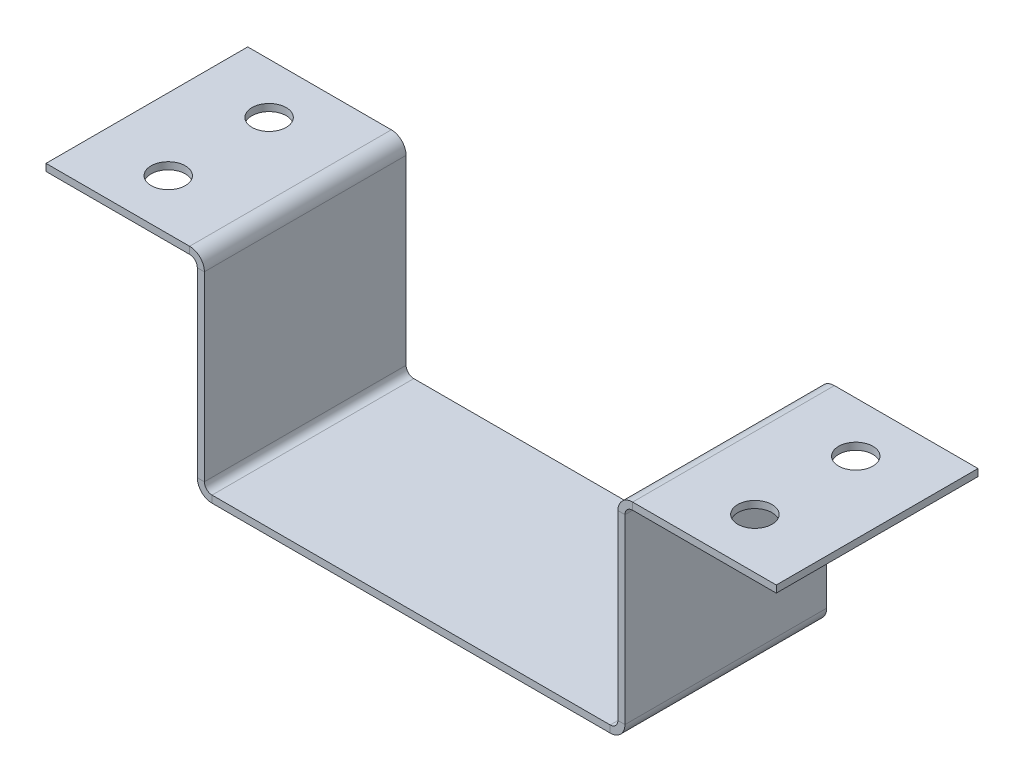
SolidWorks part; units mm, degrees
note: The reader was unsure of these and kept them because the rebuilt part matched: flange length of "Edge-Flange1", "Edge-Flange2".
ref_plane "Front Plane" through (0, 0, 0) normal (0, 0, 1) x (1, 0, 0)
ref_plane "Top Plane" through (0, 0, 0) normal (0, 1, 0) x (1, 0, 0)
ref_plane "Right Plane" through (0, 0, 0) normal (1, 0, 0) x (0, 0, -1)
sketch "Sketch1" plane through (0, 0, 0) normal (0, 1, 0) x (1, 0, 0)
  line L1 (0, 0) -> (41, 0)
  line L2 (0, 0) -> (0, 20)
  line L3 (0, 20) -> (41, 20)
  line L4 (41, 0) -> (41, 20)
  dimension "D1" = 41
  dimension "D2" = 20
base flange "Base-Flange1" sketch "Sketch1" thickness 0.7 reverse thickness direction no parameters "D1"=0.762
ref_plane "Mid" through (20.5, 0, 0) normal (1, 0, 0) x (0, 0, -1)
edge flange "Edge-Flange1" sketch "Sketch4" flange angle 90 flange length 20.25 flange position material outside bend radius 0.762 thickness 0.7 relief rectangular parameters "D6"=10
sketch "Sketch4" plane through (41, 0, 0) normal (1, 0, 0) x (0, 0, -1)
  line L0 (0, 0) -> (20, 0) construction
  line L1 (0, 0) -> (20, 0)
  line L2 (0, 0) -> (0, 20.25)
  line L3 (0, 20.25) -> (20, 20.25)
  line L4 (20, 20.25) -> (20, 0)
bend "EdgeBend1" bend radius 0.762 bend angle 90 parameters "D5"=1
edge flange "Edge-Flange2" sketch "Sketch7" flange angle 90 flange length 15 flange position material inside bend radius 0.762 thickness 0.7 relief rectangular parameters "D6"=10
sketch "Sketch7" plane through (41.7, 20.25, 0) normal (0, 1, 0) x (0, 0, 1)
  line L0 (-20, 0) -> (0, 0) construction
  line L1 (-20, 0) -> (0, 0)
  line L2 (-20, 0) -> (-20, 15)
  line L3 (-20, 15) -> (0, 15)
  line L4 (0, 15) -> (0, 0)
bend "EdgeBend2" bend radius 0.762 bend angle 90 parameters "D5"=2
mirror "Mirror1" about plane through (20.5, 0, 0) normal (1, 0, 0) of "Edge-Flange2", "Edge-Flange1"
bend "MirrorBend1" bend radius 0.762 bend angle 90 parameters "D5"=3
bend "MirrorBend2" bend radius 0.762 bend angle 90 parameters "D5"=4
hole_wizard "M3 Clearance Hole1" positions "Sketch9" profile "Sketch8" hole size "M3" standard "ANSI Metric"
sketch "Sketch9" plane through (0, 20.25, 0) normal (0, 1, 0) x (1, 0, 0)
  line L1 (49.581, 20) -> (49.581, 0) construction
  line L2 (56.7, 20) -> (42.462, 20) construction
  line L3 (42.462, 0) -> (56.7, 0) construction
  line L5 (-8.581, 20) -> (-8.581, 0) construction
  line L6 (-15.7, 20) -> (-1.462, 20) construction
  line L7 (-1.462, 0) -> (-15.7, 0) construction
  point P0 (49.581, 15)
  point P2 (49.581, 5)
  point P4 (-8.581, 15)
  point P6 (-8.581, 5)
  dimension "D1" = 5
  dimension "D2" = 5
  dimension "D3" = 5
  dimension "D4" = 5
sketch "Sketch8" plane through (49.581, 20.25, -15) normal (1, 0, 0) x (0, 0, 1)
  line L0 (0, 0) -> (0, 1.7205)
  line L1 (0, 1.7205) -> (1.7, 0.699)
  line L2 (1.7, 0.699) -> (1.7, 0)
  line L5 (1.7, 0) -> (0, 0)
  line L10 (0, 1.7205) -> (-1.7, 0.699) construction
  line L11 (0, -6.35) -> (0, 107.95) construction
  dimension "Hole Dia." = 3.4
  dimension "Hole Depth" = 0.699
  dimension "Drill Angle" = 118
sketch "Bend-Lines1" [suppressed] plane through (0, 0, 0) normal (0, 1, 0) x (1, 0, 0)
sketch "Bounding-Box1" [suppressed] plane through (0, 0, 0) normal (0, 1, 0) x (1, 0, 0)
sheet metal parameters "Sheet-Metal(1)" thickness 0.7 parameters "D1"=0.762
flat pattern "Flat-Pattern(1)" [suppressed]
sketch "Bend-Lines2" plane through (0, 0, 0) normal (0, 1, 0) x (1, 0, 0)
sketch "Bounding-Box2" [suppressed] plane through (0, 0, 0) normal (0, 1, 0) x (1, 0, 0)
sheet metal parameters "Sheet-Metal(8)" thickness 0.7 parameters "D1"=0.762
flat pattern "Flat-Pattern(1)" [suppressed]
sketch "Bend-Lines2" plane through (0, 0, 0) normal (0, 1, 0) x (1, 0, 0)
sketch "Bounding-Box2" [suppressed] plane through (0, 0, 0) normal (0, 1, 0) x (1, 0, 0)
bend of the flat pattern "Flatten-<EdgeBend1>1"
sheet metal parameters "Sheet-Metal(9)" thickness 0.7 parameters "D1"=0.762
flat pattern "Flat-Pattern(1)" [suppressed]
sketch "Bend-Lines2" plane through (0, 0, 0) normal (0, 1, 0) x (1, 0, 0)
sketch "Bounding-Box2" [suppressed] plane through (0, 0, 0) normal (0, 1, 0) x (1, 0, 0)
bend of the flat pattern "Flatten-<EdgeBend1>1"
bend of the flat pattern "Flatten-<EdgeBend2>1"
sheet metal parameters "Sheet-Metal(10)" thickness 0.7 parameters "D1"=0.762
flat pattern "Flat-Pattern(1)" [suppressed]
sketch "Bend-Lines2" plane through (0, 0, 0) normal (0, 1, 0) x (1, 0, 0)
sketch "Bounding-Box2" [suppressed] plane through (0, 0, 0) normal (0, 1, 0) x (1, 0, 0)
bend of the flat pattern "Flatten-<EdgeBend1>1"
bend of the flat pattern "Flatten-<EdgeBend2>1"
bend of the flat pattern "Flatten-<MirrorBend1>1"
bend of the flat pattern "Flatten-<MirrorBend2>1"
sheet metal parameters "Sheet-Metal(11)" thickness 0.7 parameters "D1"=0.762
flat pattern "Flat-Pattern(1)"
sketch "Bend-Lines2" plane through (0, 0, 0) normal (0, 1, 0) x (1, 0, 0)
  line L0 (-19.701, 20) -> (-19.701, 0) construction
  line L1 (-0.0503, 20) -> (-0.0503, 0) construction
  line L2 (60.701, 0) -> (60.701, 20) construction
  line L3 (41.0503, 0) -> (41.0503, 20) construction
  line L4 (-19.701, 20) -> (-19.701, 0) construction
  line L5 (-0.0503, 20) -> (-0.0503, 0) construction
  line L6 (60.701, 0) -> (60.701, 20) construction
  line L7 (41.0503, 0) -> (41.0503, 20) construction
sketch3d "Bounding-Box2" [suppressed]
  line L0 (75.7513, 20, 0) -> (-34.7513, 20, 0) construction
  line L1 (75.7513, 0, 0) -> (-34.7513, 0, 0) construction
  line L2 (75.7513, 20, 0) -> (75.7513, 0, 0) construction
  line L3 (-34.7513, 20, 0) -> (-34.7513, 0, 0) construction
bend of the flat pattern "Flatten-<EdgeBend1>1"
bend of the flat pattern "Flatten-<EdgeBend2>1"
bend of the flat pattern "Flatten-<MirrorBend1>1"
bend of the flat pattern "Flatten-<MirrorBend2>1"
